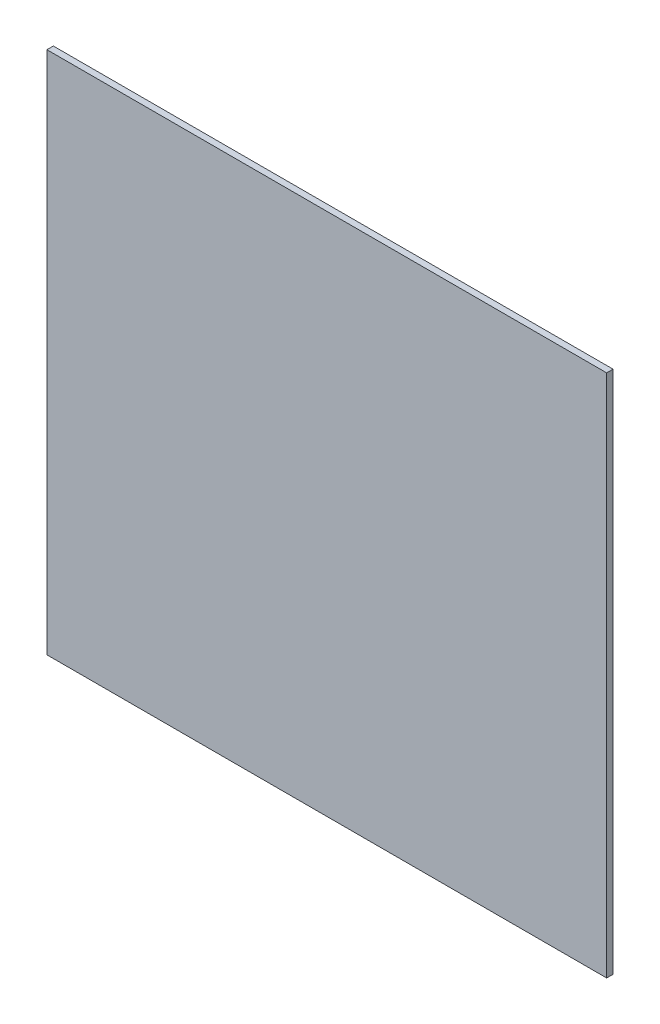
SolidWorks part; units mm, degrees
ref_plane "Спереди" through (0, 0, 0) normal (0, 0, 1) x (1, 0, 0)
ref_plane "Сверху" through (0, 0, 0) normal (0, 1, 0) x (1, 0, 0)
ref_plane "Справа" through (0, 0, 0) normal (1, 0, 0) x (0, 0, -1)
other "Configuration Table"
sketch "Эскиз1" plane through (0, 0, 0) normal (0, 0, 1) x (1, 0, 0)
  line L0 (0, -484.6) -> (-524, -484.6) construction
  line L1 (0, -484.6) -> (-524, -484.6)
  line L2 (0, -484.6) -> (0, 6)
  line L3 (0, 6) -> (-524, 6)
  line L4 (-524, -484.6) -> (-524, 6)
  line L5 (0, 6) -> (-518, 6) construction
  line L6 (0, 6) -> (0, -484.6) construction
  line L7 (-524, -866.6) -> (-524, 6) construction
extrude "Бобышка-Вытянуть1" add sketch "Эскиз1" against normal blind 6
equation "\"Толщина стенки\" = 6"
equation "\"Ширина груза\"= 420"
equation "\"Глубина груза\"= 490"
equation "\"Высота груза\"= 297"
equation "\"Ширина ячейки\"= \"Ширина груза\" + 10"
equation "\"Глубина ячейки\"= \"Глубина груза\" + 10"
equation "\"Высота ячейки\"= \"Высота груза\" + 10 + 13"
equation "\"Колво ячеек ширина\"= 2"
equation "\"Колво ячеек высота\"= 2"
equation "\"Крепление дверцы\"= 5"
equation "\"Ширина рейки\"= \"Толщина шестерни\""
equation "\"Высота рейки\"= 20"
equation "\"Высота пола\"= 20"
equation "\"Колво полозьев\"= 5"
equation "\"Отступ рейки\"= 20"
equation "\"Глубина каретки\"= \"Глубина ячейки\" + 30 + \"Мотор Y высота корпуса\" + 20"
equation "\"Длинна рейки\"= ( \"Ширина ячейки\" + \"Толщина стенки\" + \"Крепление дверцы\" ) * \"Колво ячеек ширина\" + \"Ширина ячейки выгрузки\" * \"Колво выгрузки\" + \"Толщина стенки\""
equation "\"Отступ шпильки\"= 26"
equation "\"Диаметр шпильки\"= 5"
equation "\"Длинна шпильки\"= ( \"Высота ячейки\" + \"Толщина стенки\" + \"Высота пола\" ) * \"Колво ячеек высота\" + ( \"Толщина стенки\" + \"Отступ рейки\" ) * 2 "
equation "\"Ширина пластины\"= 50  "
equation "\"Высота зона выгрузки\"= \"Высота ячейки\" * 2 + \"Толщина стенки\" * 2"
equation "\"Колво выгрузки\"= 1"
equation "\"Ширина ячейки выгрузки\"= \"Ширина ячейки\" + \"Толщина стенки\" + \"Отступ крепления мотора фиксации\"*2"
equation "\"Отступ крепления мотора фиксации\" = 30"
equation "\"Мотор X ширина корпуса\"= 42.3"
equation "\"Мотор X высота корпуса\"= 42.3"
equation "\"Мотор X длина корпуса\"= 40"
equation "\"Мотор X вылет вала\"= 19.8"
equation "\"Мотор Y ширина корпуса\"= 42.3"
equation "\"Мотор Y высота корпуса\"= 42.3"
equation "\"Мотор Y длина корпуса\"= 48"
equation "\"Мотор Y вылет вала\"= 30"
equation "\"Мотор Z ширина корпуса\"= 42"
equation "\"Мотор Z высота корпуса\"= 42"
equation "\"Мотор Z длина корпуса\"= 40"
equation "\"Мотор Z вылет вала\"= 23"
equation "\"Мотор диаметр вала ПРЕДВ\"= 5"
equation "\"Мотор шаг крепления ПРЕДВ\"= 31"
equation "\"Мотор диаметр отверстий ПРЕДВ\"= 3"
equation "\"Мотор глубина отверстий ПРЕДВ\"= 4.5"
equation "\"Мотор диаметр буртика ПРЕДВ\"= 22"
equation "\"Мотор высота буртика ПРЕДВ\"= 2"
equation "\"Мотор диаметр шкива ПРЕДВ\"= 16"
equation "\"Мотор длина шкива ПРЕДВ\"= 12"
equation "\"Мотор отступ шкива ПРЕДВ\"= 5"
equation "\"Мотор X шаг градусов\"= 1.8"
equation "\"Мотор Y шаг градусов\"= 1.8"
equation "\"Мотор Z шаг градусов\"= 1.8"
equation "\"Мотор Y диаметр ротора\"= 25.78"
equation "\"Толщина шестерни\"= 10"
equation "\"D1@Бобышка-Вытянуть1\"=\"Толщина стенки\""
